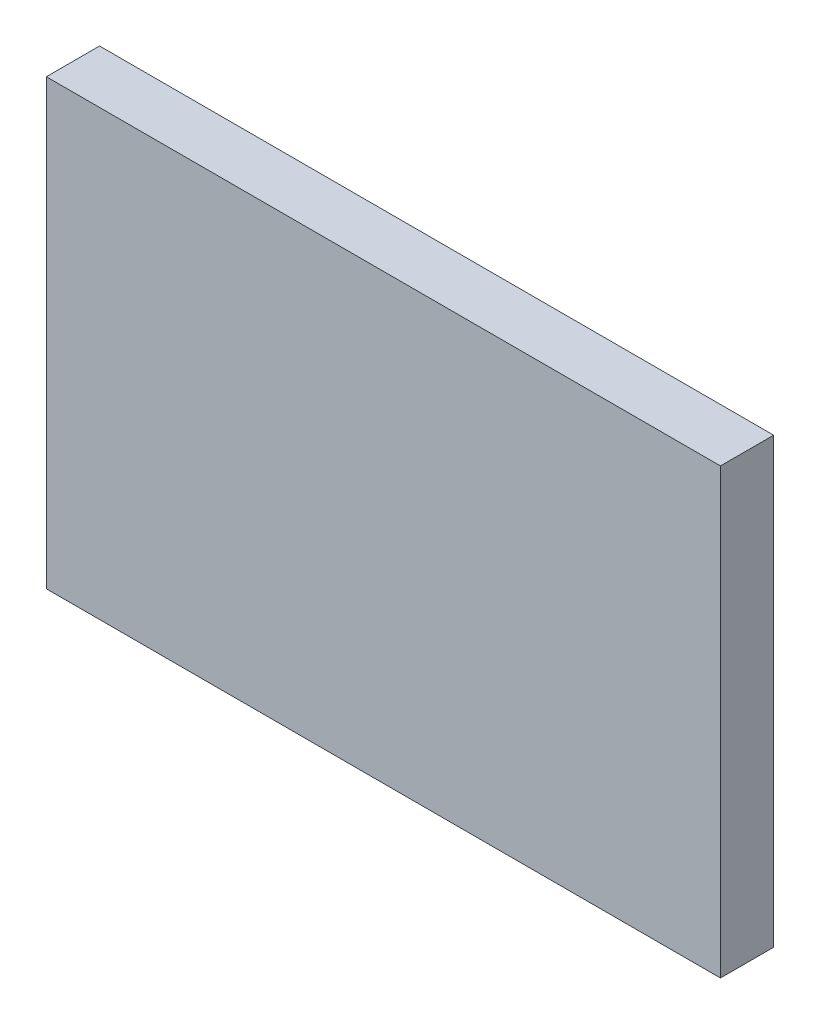
SolidWorks part; units mm, degrees
ref_plane "Front Plane" through (0, 0, 0) normal (0, 0, 1) x (1, 0, 0)
ref_plane "Top Plane" through (0, 0, 0) normal (0, 1, 0) x (1, 0, 0)
ref_plane "Right Plane" through (0, 0, 0) normal (1, 0, 0) x (0, 0, -1)
sketch "Sketch1" plane through (0, 0, 0) normal (0, 0, 1) x (1, 0, 0)
  line L7 (-19, 47.9782) -> (19, 47.9782)
  line L8 (-19, 47.9782) -> (-19, 22.9782)
  line L9 (-19, 22.9782) -> (19, 22.9782)
  line L10 (19, 47.9782) -> (19, 22.9782)
extrude "Boss-Extrude1" add sketch "Sketch1" along normal blind 3
